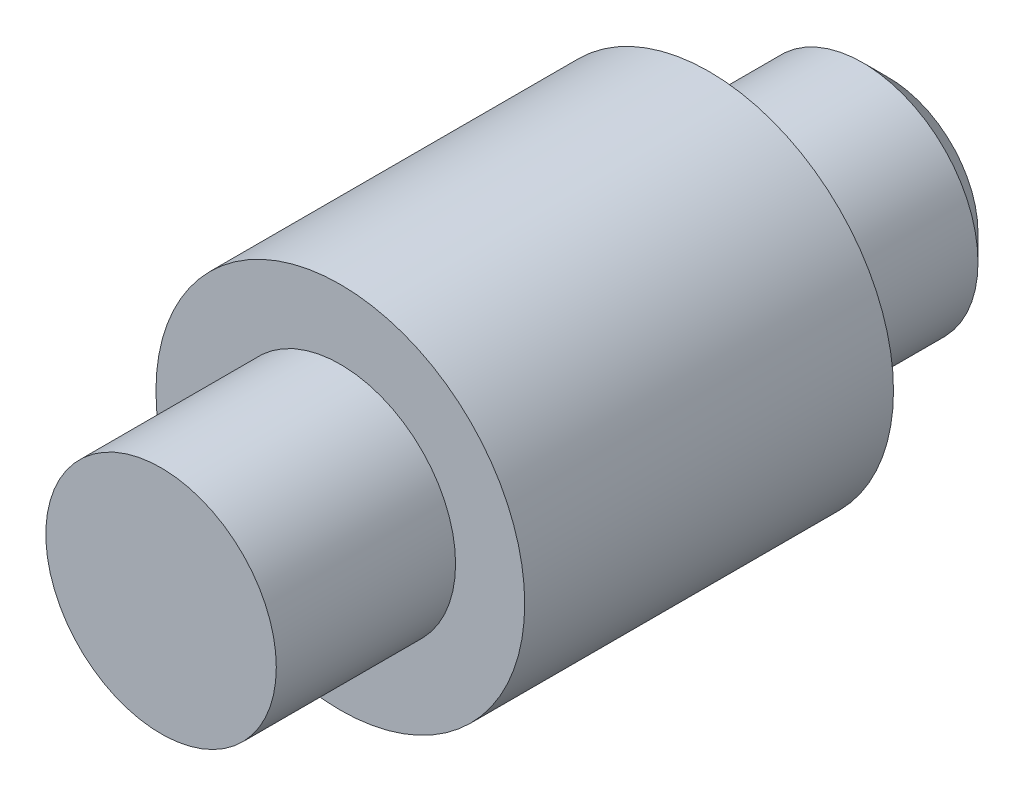
SolidWorks part; units mm, degrees
ref_plane "Front Plane" through (0, 0, 0) normal (0, 0, 1) x (1, 0, 0)
ref_plane "Top Plane" through (0, 0, 0) normal (0, 1, 0) x (1, 0, 0)
ref_plane "Right Plane" through (0, 0, 0) normal (1, 0, 0) x (0, 0, -1)
sketch "Sketch2" plane through (0, 0, 0) normal (0, 0, 1) x (1, 0, 0)
  circle A0 centre (0, 0) radius 1.25
  dimension "D1" = 2.5
sketch "Sketch3" plane through (0, 0, 0) normal (0, 0, 1) x (1, 0, 0)
  line L5 (-3.6, 3.6) -> (3.6, 3.6) construction
  line L6 (-3.6, 3.6) -> (-3.6, -3.6) construction
  line L7 (-3.6, -3.6) -> (3.6, -3.6) construction
  line L8 (3.6, 3.6) -> (3.6, -3.6) construction
  circle A0 centre (0, 0) radius 3.6
  point P4 (0, 3.6)
  point P6 (-3.6, 0)
  dimension "D1" = 7.2
extrude "Boss-Extrude1" add sketch "Sketch3" along normal blind 7.2
sketch "Sketch4" plane through (0, 0, 0) normal (0, 0, 1) x (1, 0, 0)
  circle A0 centre (0, 0) radius 2.25
  dimension "D1" = 4.5
extrude "Boss-Extrude2" add sketch "Sketch4" against normal blind 3.5
sketch "Sketch5" plane through (0, 0, 7.2) normal (0, 0, 1) x (1, 0, 0)
  circle A0 centre (0, 0) radius 2.25
  dimension "D1" = 4.5
extrude "Boss-Extrude3" add sketch "Sketch5" along normal blind 3.5
chamfer "Chamfer1" distance 0.5 angle 45 1 edges at (2.25, 0, -3.5)
equation "\"length\"=7.2"
equation "\"D1@Boss-Extrude1\"=\"length\""
equation "\"hole\"=4.5"
equation "\"D1@Sketch5\"=\"hole\""
equation "\"D1@Sketch4\"=\"hole\""
equation "\"foot\"=3.5"
equation "\"D1@Boss-Extrude3\"=\"foot\""
equation "\"D1@Boss-Extrude2\"=\"foot\""
